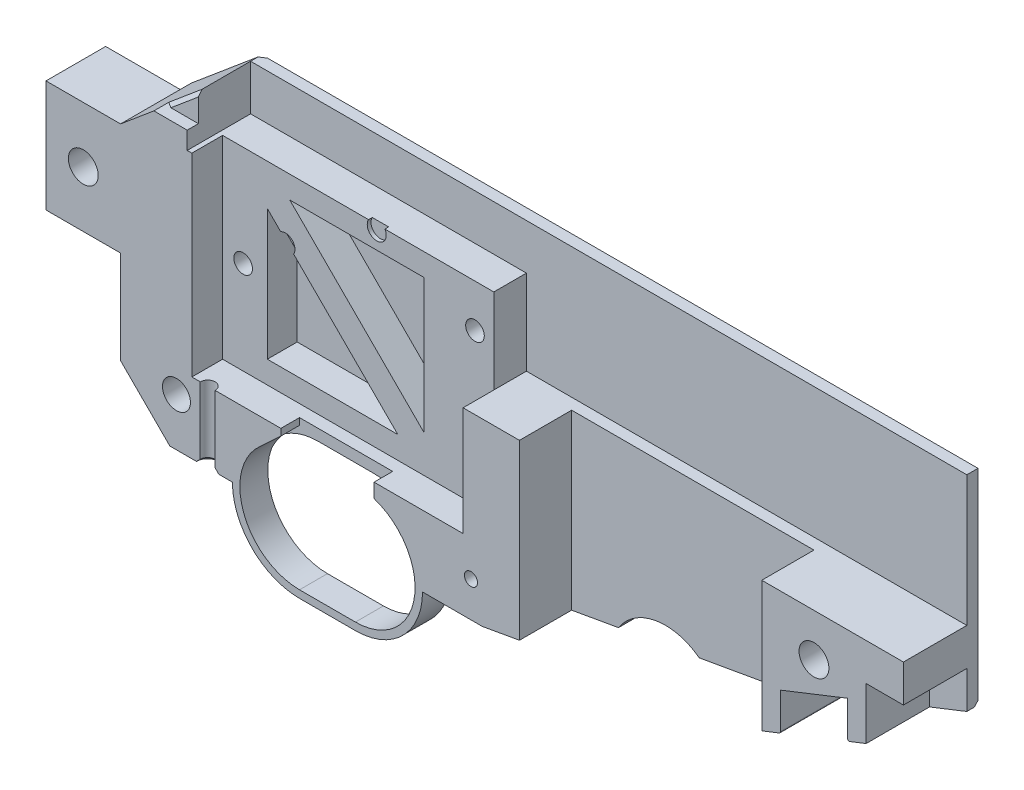
SolidWorks part; units mm, degrees
ref_plane "정면" through (0, 0, 0) normal (0, 0, 1) x (1, 0, 0)
ref_plane "윗면" through (0, 0, 0) normal (0, 1, 0) x (1, 0, 0)
ref_plane "우측면" through (0, 0, 0) normal (1, 0, 0) x (0, 0, -1)
sketch "스케치1" plane through (0, 0, 0) normal (0, 0, 1) x (1, 0, 0)
  line L0 (0, 0) -> (20, 0)
  line L1 (20, 0) -> (37.8763, 15)
  line L2 (37.8763, 15) -> (230, 15)
  line L3 (230, 15) -> (230, -54.9955)
  line L4 (230, -54.9955) -> (192, -54.9955)
  line L5 (0, 0) -> (0, -30)
  line L6 (0, -30) -> (20, -30)
  line L7 (20, -30) -> (20, -55)
  line L8 (20, -55) -> (33.22, -68.22)
  line L9 (33.22, -68.22) -> (50, -68.22)
  line L10 (68, -68.22) -> (83, -68.22) construction
  line L11 (68, -52.22) -> (83, -52.22)
  line L12 (68, -84.22) -> (83, -84.22)
  line L13 (67.2987, -49.22) -> (82.2987, -49.22)
  line L14 (139.5521, -64.2435) -> (117, -68.22)
  line L15 (101, -68.22) -> (117, -68.22)
  line L16 (117, -68.22) -> (192, -54.9955) construction
  line L17 (68, -86.22) -> (83, -86.22)
  line L18 (161.2179, -60.4232) -> (192, -54.9955)
  line L20 (68, -50.22) -> (83, -50.22) construction
  arc A0 (68, -52.22) -> (68, -84.22) centre (68, -68.22) ccw
  arc A1 (83, -84.22) -> (83, -52.22) centre (83, -68.22) ccw
  arc A3 (68, -50.22) -> (68, -86.22) centre (68, -68.22) ccw construction
  arc A4 (83, -86.22) -> (101, -68.22) centre (83, -68.22) ccw
  arc A5 (83, -86.22) -> (83, -50.22) centre (83, -68.22) ccw construction
  arc A6 (161.2179, -60.4232) -> (139.5521, -64.2435) centre (152.1559, -72.3764) ccw
  arc A7 (50, -68.22) -> (68, -86.22) centre (68, -68.22) ccw
  point P14 (75.5, -68.22)
  point P19 (80.5569, -40.2571)
  point P20 (93.5569, -40.2571)
  point P21 (93.5569, -59.2571)
  point P22 (93.5569, -78.2571)
  point P23 (80.5569, -78.2571)
  point P24 (80.5569, -59.2571)
  point P25 (50, -68.22)
  point P26 (101, -68.22)
  point P39 (139.5521, -64.2435)
  point P40 (161.2179, -60.4232)
  dimension "D4" = 16
  dimension "D13" = 16
  dimension "D14" = 15
  dimension "D1" = 230
  dimension "D2" = 30
  dimension "D3" = 15
  dimension "D6" = 2
  dimension "D5" = 16
  dimension "D7" = 3
  dimension "D8" = 135
  dimension "D9" = 64.22
  dimension "D10" = 140
  dimension "D11" = 170
  dimension "D12" = 15
  dimension "D15" = 30
  dimension "D16" = 75
  dimension "D17" = 51
  dimension "D18" = 22
  dimension "D19" = 20
  dimension "D20" = 25
  dimension "D21" = 22.9
  dimension "D22" = 20
extrude "보스-돌출1" add sketch "스케치1" along normal blind 20 contours L9 A7 L17 A4 L15 L16 L4 L3 L2 L1 L0 L5 L6 L7 L8 A1 L12 A0 L11 region at (119.6066, -23.0148, 0)
sketch "스케치2" plane through (0, 0, 20) normal (0, 0, 1) x (1, 0, 0)
  line L0 (68, -52.22) -> (83, -52.22) construction
  line L1 (39.125, 2.78) -> (111.875, 2.78)
  line L2 (39.125, 2.78) -> (39.125, -49.22)
  line L3 (39.125, -49.22) -> (111.875, -49.22)
  line L4 (111.875, 2.78) -> (111.875, -49.22)
  line L5 (75.5, -52.22) -> (75.5, -49.22) construction
  point P6 (75.5, -52.22)
  point P9 (75.5, -49.22)
  dimension "D1" = 52
  dimension "D2" = 72.75
  dimension "D3" = 3
extrude "컷-돌출1" cut sketch "스케치2" against normal blind 8.25
sketch "스케치3" plane through (0, 0, 20) normal (0, 0, 1) x (1, 0, 0)
  line L1 (37.8763, 2.78) -> (37.8763, 15)
  line L2 (37.8763, 15) -> (211, 15)
  line L5 (37.8763, 2.78) -> (211, 2.78)
  line L6 (211, 15) -> (211, 2.78)
  line L8 (211, -54.9955) -> (211, 15) construction
  line L9 (230, -54.9955) -> (192, -54.9955) construction
  line L10 (37.8763, 15) -> (230, 15) construction
  dimension "D1" = 12.22
extrude "컷-돌출4" cut sketch "스케치3" against normal blind 17
sketch "스케치5" plane through (0, 0, 20) normal (0, 0, 1) x (1, 0, 0)
  line L0 (192, -54.9955) -> (161.2179, -60.4232)
  line L1 (127, 2.0106) -> (192, 2.0088)
  line L2 (127, 2.0106) -> (127, -66.6451)
  line L4 (192, 2.0088) -> (192, -54.9955)
  line L5 (161.2179, -60.4232) -> (192, -54.9955) construction
  line L6 (127, -66.6451) -> (139.5521, -64.2435)
  arc A0 (139.5521, -64.2435) -> (161.2179, -60.4232) centre (152.1559, -72.3764) cw
  dimension "D1" = 10
extrude "컷-돌출5" cut sketch "스케치5" against normal blind 14
sketch "스케치6" plane through (0, 0, 20) normal (0, 0, 1) x (1, 0, 0)
  line L1 (63, -49.22) -> (88, -49.22)
  line L2 (39.125, -49.22) -> (111.875, -49.22) construction
  line L3 (68, -52.22) -> (83, -52.22)
  line L4 (88, -49.22) -> (88, -53.0213)
  line L5 (63, -49.22) -> (63, -53.0213)
  arc A0 (68, -52.22) -> (68, -84.22) centre (68, -68.22) ccw construction
  arc A1 (83, -84.22) -> (83, -52.22) centre (83, -68.22) ccw construction
  arc A2 (68, -52.22) -> (63, -53.0213) centre (68, -68.22) ccw
  arc A3 (88, -53.0213) -> (83, -52.22) centre (83, -68.22) ccw
  point P2 (75.5, -49.22)
  dimension "D1" = 25
extrude "컷-돌출6" cut sketch "스케치6" against normal blind 5
sketch "스케치7" plane through (0, -86.22, 0) normal (0, -1, 0) x (1, 0, 0)
  line L0 (75.5, 12.5) -> (93.5, 12.5)
  line L3 (75.5, 0) -> (101, 0)
  line L4 (75.5, 12.5) -> (50, 12.5)
  line L5 (75.5, 0) -> (75.5, 12.5)
  line L8 (50, 12.5) -> (50, 0)
  line L9 (93.5, 12.5) -> (101, 12.5)
  line L11 (101, 12.5) -> (101, 0)
  line L12 (50, 0) -> (75.5, 0)
  line M6 (68, 0) -> (83, 0)
  line M7 (83, 0) -> (83, 20)
  line M9 (68, 20) -> (68, 0)
  dimension "D1" = 12.5
extrude "컷-돌출7" cut sketch "스케치7" against normal up to surface (18 mm away) contours L5 L0 M6 M7 | L11 L9 L0 L3 M7 region at (79.25, -86.22, 6.25) region at (92, -86.22, 6.25) up to face at (109, -68.22, 10)
sketch "스케치11" plane through (0, 0, 0) normal (0, 0, -1) x (-1, 0, 0)
  line L0 (-50, -68.22) -> (-50, -42.5)
  line L1 (-50, -42.5) -> (-20, -42.5)
  line L2 (-20, -30) -> (-20, -55) construction
  line L3 (-20, -42.5) -> (-20, -55)
  line L4 (-20, -55) -> (-33.22, -68.22)
  line L5 (-33.22, -68.22) -> (-50, -68.22)
extrude "컷-돌출13" cut sketch "스케치11" against normal blind 8
sketch "스케치12" plane through (0, 0, 8) normal (0, 0, -1) x (-1, 0, 0)
  line L0 (-41.61, -68.22) -> (-41.61, -55.36)
  line L1 (-50, -68.22) -> (-33.22, -68.22) construction
  line L2 (-41.61, -55.36) -> (-50, -55.36)
  line L3 (-50, -42.5) -> (-50, -68.22) construction
  line L4 (-50, -55.36) -> (-50, -68.22)
  line L5 (-50, -68.22) -> (-41.61, -68.22)
extrude "컷-돌출15" cut sketch "스케치7<4>" against normal up to vertex (30.86 mm away) contours L5 L4 M6 M9 | L8 L12 L4 M9 region at (71.75, -86.22, 6.25) region at (59, -86.22, 6.25) up to point (50, -55.36, 8)
sketch "스케치7<4>" plane through (0, -86.22, 0) normal (0, -1, 0) x (1, 0, 0) same geometry as "스케치7"
fillet "필렛3" radius 7.5 1 edges at (54.2403, -55.36, 12.5) second distance 9 first distance on face at (72.5955, -74.4968, 12.5)
extrude "컷-돌출16" cut sketch "스케치12" against normal blind 6 contours L2 L4 L5 L0
chamfer "모따기4" distance 1 angle 45 1 edges at (41.61, -68.22, 11)
fillet "필렛4" radius 6 1 edges at (100, -68.22, 12.5) second distance 8 first distance on face at (105.6667, -68.22, 10.8333)
sketch "스케치13" plane through (0, 0, 20) normal (0, 0, 1) x (1, 0, 0)
  line L1 (230, 15) -> (111.87, 15)
  line L2 (230, 15) -> (230, -20)
  line L3 (230, -20) -> (111.87, -20)
  line L4 (111.87, 15) -> (111.87, -20)
  dimension "D1" = 35
  dimension "D2" = 118.13
extrude "컷-돌출17" cut sketch "스케치13" against normal blind 17
sketch "스케치14" plane through (0, 0, 20) normal (0, 0, 1) x (1, 0, 0)
  line L1 (230, -54.9955) -> (220, -54.9955)
  line L2 (230, -54.9955) -> (230, -29.9955)
  line L3 (230, -29.9955) -> (220, -29.9955)
  line L4 (220, -54.9955) -> (220, -29.9955)
  dimension "D1" = 10
  dimension "D2" = 25
extrude "컷-돌출18" cut sketch "스케치14" against normal blind 17
sketch "스케치16" plane through (0, 0, 0) normal (0, 0, -1) x (-1, 0, 0)
  line L0 (-192, -54.9955) -> (-230, -39.9955)
  line L1 (-230, 15) -> (-230, -54.9955) construction
  line L2 (-230, -39.9955) -> (-230, -54.9955)
  line L3 (-230, -54.9955) -> (-192, -54.9955)
  dimension "D1" = 15
extrude "컷-돌출19" cut sketch "스케치16" against normal up to next
sketch "스케치18" plane through (0, 0, 20) normal (0, 0, 1) x (1, 0, 0)
  line L0 (101, -68.22) -> (127, -49.22) construction
  line L1 (127, -20) -> (127, -66.4567) construction
  circle A0 centre (114, -58.72) radius 1.75
  dimension "D1" = 3.5
sketch "스케치21" plane through (0, 0, 8) normal (0, 0, -1) x (-1, 0, 0)
  line L0 (-50, -68.22) -> (-20, -42.5) construction
  circle A0 centre (-35, -55.36) radius 3.75
  dimension "D1" = 7.5
extrude "컷-돌출23" cut sketch "스케치21" against normal up to next
sketch "스케치24" plane through (0, 0, 0) normal (0, 0, -1) x (-1, 0, 0)
  line L1 (0, 0) -> (-20, 0)
  line L2 (0, 0) -> (0, -30)
  line L3 (0, -30) -> (-20, -30)
  line L4 (-20, 0) -> (-20, -30)
extrude "컷-돌출26" cut sketch "스케치24" against normal blind 4
sketch "스케치25" plane through (0, 0, 0) normal (0, 0, -1) x (-1, 0, 0)
  line L0 (-117, -68.22) -> (-117, -13.2245)
  line L1 (-189, -28.0267) -> (-120, -40.1933)
  line L2 (-192, 0) -> (-192, -54.9955)
  line L3 (-139.5521, -64.2435) -> (-117, -68.22) construction
  line L4 (-161.2179, -60.4232) -> (-192, -54.9955) construction
  line L5 (-161.2179, -60.4232) -> (-192, -54.9955)
  line L6 (-139.5521, -64.2435) -> (-117, -68.22)
  line L7 (-120, -64.6447) -> (-120, -15.7418)
  line L8 (-189, -3.5753) -> (-120, -15.7418)
  line L9 (-189, -3.5753) -> (-189, -52.4782)
  line L10 (-161.9179, -57.2535) -> (-189, -52.4782)
  line L11 (-137.8102, -61.5043) -> (-120, -64.6447)
  line L12 (-192, 0) -> (-117, -13.2245)
  line L13 (-189, -3) -> (-189, -52.4782) construction
  line L14 (-120, -64.6447) -> (-120, -3) construction
  line L15 (-117, -68.22) -> (-117, 0) construction
  line L16 (-120, -3) -> (-189, -3) construction
  line L17 (-117, 0) -> (-192, 0) construction
  line L18 (-189, -30.9811) -> (-120, -43.1477)
  line L19 (-189, -25.0723) -> (-120, -37.2389)
  line L20 (-189, -28.0267) -> (-194.8846, -26.9891)
  line L21 (-120, -40.1933) -> (-111.0757, -41.7669)
  line L22 (-120, -15.7418) -> (-189, -15.7418)
  arc A0 (-139.5521, -64.2435) -> (-161.2179, -60.4232) centre (-152.1559, -72.3764) ccw construction
  arc A1 (-139.5521, -64.2435) -> (-161.2179, -60.4232) centre (-152.1559, -72.3764) ccw
  arc A2 (-137.8102, -61.5043) -> (-161.9179, -57.2535) centre (-152.1559, -72.3764) ccw
  point P17 (-192.5209, -2.9544)
  point P18 (-117.5209, -16.1789)
  dimension "D1" = 3
extrude "컷-돌출27" cut sketch "스케치25" against normal blind 2 contours A2 L11 L7 L9 L10 | L9 L19 L7 L8 region at (154.7863, -47.2575, 0) region at (149.9613, -23.8488, 0)
fillet "필렛6" radius 1 19 edges at (128.9051, -63.0745, 0) (128.9051, -63.0745, 2) (149.0302, -54.6499, 0) (149.0302, -54.6499, 2) (175.4589, -54.8658, 0) (175.4589, -54.8658, 2) (189, -41.7297, 0) (189, -41.7297, 2) (120, -53.8962, 0) (120, -53.8962, 2) (154.5, -37.0644, 0) (154.5, -31.1556, 0) (189, -20.4071, 2) (120, -26.4903, 2) (154.5, -31.1556, 2) (154.5, -37.0644, 2) (189, -20.4071, 0) (154.5, -15.7418, 0) (154.5, -15.7418, 2)
sketch "스케치29" plane through (37.8763, 0, 0) normal (1, 0, 0) x (0, 0, -1)
  line L1 (-20, 15) -> (-17, 15)
  line L2 (-20, 15) -> (-20, 7.5)
  line L3 (-20, 7.5) -> (-17, 7.5)
  line L4 (-17, 15) -> (-17, 7.5)
  dimension "D1" = 3
  dimension "D2" = 7.5
extrude "컷-돌출28" cut sketch "스케치29" against normal blind 10
chamfer "모따기6" distance 1 angle 45 1 edges at (33.4072, 11.25, 17)
sketch "스케치30" plane through (0, -68.22, 0) normal (0, -1, 0) x (1, 0, 0)
  line L0 (33.22, 20) -> (50, 20) construction
  circle A0 centre (43.375, 20) radius 2
  dimension "D2" = 4
  dimension "D1" = 6.625
extrude "컷-돌출29" cut sketch "스케치30" against normal through all
chamfer "모따기7" distance 1 angle 45 1 edges at (43.375, -68.22, 18)
sketch "스케치32" plane through (0, 0, 4) normal (0, 0, -1) x (-1, 0, 0)
  line L0 (0, 0) -> (-20, -30) construction
  circle A0 centre (-10, -15) radius 4
  dimension "D1" = 8
extrude "컷-돌출30" cut sketch "스케치32" against normal through all
sketch "스케치35" plane through (0, 0, 11.75) normal (0, 0, 1) x (1, 0, 0)
  line L0 (39.125, 2.78) -> (39.125, -49.22) construction
  line L1 (39.125, -49.22) -> (111.875, -49.22) construction
  circle A0 centre (44.625, -24.22) radius 2.5
  dimension "D1" = 5
  dimension "D2" = 5.5
  dimension "D3" = 25
extrude "컷-돌출33" cut sketch "스케치35" against normal up to next
sketch "스케치36" plane through (0, 0, 11.75) normal (0, 0, 1) x (1, 0, 0)
  line L0 (39.125, -49.22) -> (111.875, -49.22) construction
  line L1 (111.87, 2.78) -> (111.87, -20) construction
  circle A0 centre (106.817, -8.72) radius 2.5
  dimension "D3" = 5
  dimension "D1" = 40.5
  dimension "D2" = 5.053
extrude "컷-돌출34" cut sketch "스케치36" against normal up to next
sketch "스케치39" plane through (0, 0, 11.75) normal (0, 0, 1) x (1, 0, 0)
  line L0 (39.125, -49.22) -> (111.875, -49.22) construction
  line L1 (51.125, -3.22) -> (93.125, -3.22)
  line L2 (51.125, -3.22) -> (51.125, -43.22)
  line L3 (51.125, -43.22) -> (93.125, -43.22)
  line L4 (93.125, -3.22) -> (93.125, -43.22)
  line L5 (39.125, 2.78) -> (39.125, -49.22) construction
  line L6 (51.125, -8.22) -> (86.125, -43.22)
  line L7 (57.125, -3.22) -> (93.125, -39.22)
  dimension "D1" = 6
  dimension "D2" = 12
  dimension "D3" = 42
  dimension "D4" = 45
  dimension "D5" = 45
  dimension "D6" = 40
  dimension "D7" = 4
  dimension "D8" = 35
extrude "컷-돌출37" cut sketch "스케치39" against normal blind 8 contours L6 L2 L3 | L1 L7 L4 region at (81.125, -15.22, 11.75) region at (62.7917, -31.5533, 11.75)
chamfer "모따기10" distance 1 angle 45 10 edges at (54.2403, -55.36, 0) (62.988, -53.0253, 0) (75.5, -52.22, 0) (94.3137, -56.9063, 0) (108, -68.22, 0) (128.276, -66.2317, 0) (149.5511, -57.6043, 0) (176.6089, -57.7093, 0) (211, -47.4955, 0) (28.9382, 7.5, 0)
chamfer "모따기11" distance 2 angle 47 1 edges at (63, -53.0213, 17.5) first distance on face at (63, -51.1207, 17.5)
sketch "스케치40" plane through (0, 0, 11.75) normal (0, 0, 1) x (1, 0, 0)
  line L0 (39.125, 2.78) -> (39.125, -49.22) construction
  line L1 (39.125, -49.22) -> (111.875, -49.22) construction
  line L2 (111.87, 2.78) -> (111.87, -20) construction
  line L3 (111.87, 2.78) -> (39.125, 2.78) construction
  circle A0 centre (55.976, -14.01) radius 2.55
  circle A1 centre (80.467, 1.49) radius 2.55
  dimension "D1" = 5.1
  dimension "D6" = 5.1
  dimension "D2" = 16.851
  dimension "D3" = 35.21
  dimension "D4" = 31.403
  dimension "D5" = 1.29
extrude "컷-돌출38" cut sketch "스케치40" against normal blind 1
sketch "스케치42" plane through (0, 0, 0) normal (0, 0, -1) x (-1, 0, 0)
  line L0 (-111.87, -20) -> (-230, -20) construction
  line L1 (-215, -25) -> (-197, -25)
  line L2 (-215, -25) -> (-215, -63.3849)
  line L3 (-215, -63.3849) -> (-197, -63.3849)
  line L4 (-197, -25) -> (-197, -63.3849)
  line L5 (-192, -54.9955) -> (-192, -20) construction
  dimension "D1" = 5
  dimension "D2" = 5
  dimension "D3" = 18
extrude "컷-돌출39" cut sketch "스케치42" against normal blind 12
extrude "컷-돌출41" cut sketch "스케치18" against normal blind 8.5 contours A0
sketch "스케치44" plane through (0, 0, 11.5) normal (0, 0, 1) x (1, 0, 0)
  circle A0 centre (114, -58.72) radius 1
  dimension "D1" = 2
extrude "컷-돌출42" cut sketch "스케치44" against normal through all
sketch "스케치45" plane through (0, 0, 12) normal (0, 0, -1) x (-1, 0, 0)
  line L0 (-215, -35.9165) -> (-197, -43.0218)
  line L1 (-215, -25) -> (-215, -45.9165) construction
  line L2 (-197, -53.0218) -> (-197, -25) construction
  line L3 (-215, -45.9165) -> (-197, -53.0218) construction
  line L4 (-197, -43.0218) -> (-197, -53.0218)
  line L5 (-197, -53.0218) -> (-215, -45.9165)
  line L6 (-215, -45.9165) -> (-215, -35.9165)
  dimension "D1" = 10
extrude "컷-돌출43" cut sketch "스케치45" against normal up to next
fillet "필렛8" radius 0.5 2 edges at (197, -53.0218, 10.5) (215, -45.9165, 10.5)
sketch "스케치47" plane through (0, 0, 12) normal (0, 0, -1) x (-1, 0, 0)
  line L0 (-215, -27.9165) -> (-197, -35.0218) construction
  line L1 (-215, -25) -> (-215, -35.9165) construction
  line L2 (-197, -43.0218) -> (-197, -25) construction
  line L3 (-197, -43.0218) -> (-215, -35.9165) construction
  circle A0 centre (-206, -31.4692) radius 4
  dimension "D2" = 8
  dimension "D1" = 8
extrude "컷-돌출44" cut sketch "스케치47" against normal up to next
fillet "필렛9" radius 1 1 edges at (202, -31.4692, 12)
